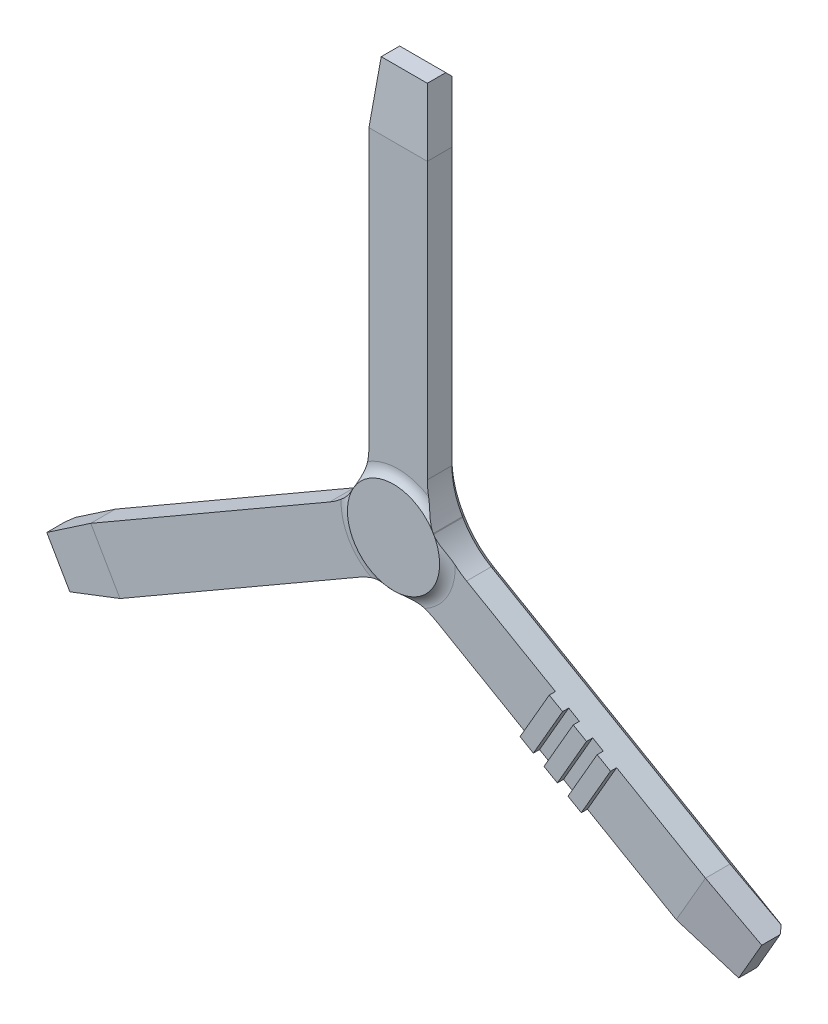
SolidWorks part; units mm, degrees
ref_plane "Front Plane" through (0, 0, 0) normal (0, 0, 1) x (1, 0, 0)
ref_plane "Top Plane" through (0, 0, 0) normal (0, 1, 0) x (1, 0, 0)
ref_plane "Right Plane" through (0, 0, 0) normal (1, 0, 0) x (0, 0, -1)
sketch "Sketch1" plane through (0, 0, 0) normal (0, 0, 1) x (1, 0, 0)
  line L0 (-1.9, 24) -> (1.9, 24) construction
  line L1 (0, 0) -> (0, 24) construction
  line L2 (-1.9, 24) -> (-1.9, 26)
  line L3 (-1.9, 26) -> (1.9, 26)
  line L4 (1.9, 26) -> (1.9, 24)
  line L5 (23.4667, -11.3546) -> (21.5667, -14.6454)
  line L6 (21.5667, -14.6454) -> (19.8346, -13.6454)
  line L7 (21.7346, -10.3546) -> (23.4667, -11.3546)
  line L8 (-21.5667, -14.6454) -> (-23.4667, -11.3546)
  line L9 (-23.4667, -11.3546) -> (-21.7346, -10.3546)
  line L10 (-19.8346, -13.6454) -> (-21.5667, -14.6454)
  line L11 (0, 0) -> (1.9, 24) construction
  line L12 (0, 0) -> (19.8346, -13.6454) construction
  line L13 (-1.9, 24) -> (-1.9, 1.097)
  line L14 (-1.9, 1.097) -> (-21.7346, -10.3546)
  line L15 (-19.8346, -13.6454) -> (0, -2.1939)
  line L16 (0, -2.1939) -> (19.8346, -13.6454)
  line L17 (21.7346, -10.3546) -> (1.9, 1.097)
  line L18 (1.9, 1.097) -> (1.9, 24)
  circle A0 centre (0, 0) radius 24 construction
  dimension "D1" = 48
  dimension "D2" = 3.8
  dimension "D3" = 2
  dimension "D4" = 120
  dimension "D5" = 24.0751
  dimension "D6" = 3
extrude "Boss-Extrude1" add sketch "Sketch1" along normal blind 2 contours L18 A0 L13 L14 L15 L16 L17 region at (0, 0, 0)
chamfer "Chamfer1" distance 4 distance2 0.4 3 edges at (22.5167, -13, 2) (-22.5167, -13, 2) (0, 26, 2) first distance on face at (0, 0, 2)
chamfer "Chamfer2" distance 0.4 distance2 4 3 edges at (23.4667, -11.3546, 0.8) (-1.9, 26, 0.8) (-21.5667, -14.6454, 0.8) first distance on face at (22.5167, -13, 0.8) first distance on face at (0, 26, 0.8) first distance on face at (-22.5167, -13, 0.8)
chamfer "Chamfer3" distance 4 distance2 0.4 3 edges at (1.9, 26, 0.8) (21.5667, -14.6454, 0.8) (-23.4667, -11.3546, 0.8) first distance on face at (1.9, 15.2388, 1.12) first distance on face at (12.2472, -9.2648, 1.12) first distance on face at (-14.1472, -5.9739, 1.12)
sketch "Sketch2" plane through (0, 0, 0) normal (0, 0, -1) x (-1, 0, 0)
  circle A0 centre (0, 0) radius 3
  dimension "D1" = 6
extrude "Boss-Extrude2" add sketch "Sketch2" against normal blind 2.3
fillet "Fillet1" radius 5 6 edges at (1.9, 2.3216, 1) (2.9606, 0.4846, 1) (1.0606, -2.8063, 1) (-1.0606, -2.8063, 1) (-2.9606, 0.4846, 1) (-1.9, 2.3216, 1)
fillet "Fillet2" radius 1 3 edges at (0, 3, 2) (2.5981, -1.5, 2) (-2.5981, -1.5, 2)
chamfer "Chamfer4" distance 0.4 angle 45 18 edges at (22.5167, -13, 0) (-22.5167, -13, 0) (0, 26, 0) (12.2293, -4.8667, 0) (3.4082, 0.4282, 0) (2.5981, 1.5, 0) (2.0749, 2.7374, 0) (1.9, 13.0242, 0) (-12.2293, -4.8667, 0) (-3.4082, 0.4282, 0) (-2.5981, 1.5, 0) (-2.0749, 2.7374, 0) (-1.9, 13.0242, 0) (10.3293, -8.1576, 0) (1.3332, -3.1657, 0) (0, -3, 0) (-1.3332, -3.1657, 0) (-10.3293, -8.1576, 0)
sketch "Sketch3" plane through (0, 0, 2) normal (0, 0, 1) x (1, 0, 0)
  line L0 (12.2293, -4.8667) -> (10.3293, -8.1576) construction
  line L3 (20.0026, -9.3546) -> (4.4561, -0.3788) construction
  line L5 (2.5561, -3.6697) -> (18.1026, -12.6454) construction
  line L7 (11.7963, -4.6167) -> (9.8963, -7.9076)
  line L8 (11.7963, -4.6167) -> (12.6623, -5.1167)
  line L9 (9.8963, -7.9076) -> (10.7623, -8.4076)
  line L10 (12.6623, -5.1167) -> (10.7623, -8.4076)
  line L11 (11.7963, -4.6167) -> (10.7623, -8.4076) construction
  line L12 (9.8963, -7.9076) -> (12.6623, -5.1167) construction
  line L13 (13.3551, -5.5167) -> (14.2212, -6.0167)
  line L14 (13.3551, -5.5167) -> (11.4551, -8.8076)
  line L15 (14.2212, -6.0167) -> (12.3212, -9.3076)
  line L16 (11.4551, -8.8076) -> (12.3212, -9.3076)
  line L29 (10.2375, -3.7167) -> (11.1035, -4.2167)
  line L30 (10.2375, -3.7167) -> (8.3375, -7.0076)
  line L31 (11.1035, -4.2167) -> (9.2035, -7.5076)
  line L32 (8.3375, -7.0076) -> (9.2035, -7.5076)
  line L465 (18.0317, -8.2167) -> (18.8977, -8.7167) [skipped]
  line L466 (18.0317, -8.2167) -> (16.1317, -11.5076) [skipped]
  line L467 (18.8977, -8.7167) -> (16.9977, -12.0076) [skipped]
  line L468 (16.1317, -11.5076) -> (16.9977, -12.0076) [skipped]
  line L469 (5.5609, -1.0167) -> (6.4269, -1.5167) [skipped]
  line L470 (5.5609, -1.0167) -> (3.6609, -4.3076) [skipped]
  line L471 (6.4269, -1.5167) -> (4.5269, -4.8076) [skipped]
  line L472 (3.6609, -4.3076) -> (4.5269, -4.8076) [skipped]
  line L473 (16.4728, -7.3167) -> (17.3389, -7.8167) [skipped]
  line L474 (16.4728, -7.3167) -> (14.5728, -10.6076) [skipped]
  line L475 (17.3389, -7.8167) -> (15.4389, -11.1076) [skipped]
  line L476 (14.5728, -10.6076) -> (15.4389, -11.1076) [skipped]
  line L477 (7.1198, -1.9167) -> (7.9858, -2.4167) [skipped]
  line L478 (7.1198, -1.9167) -> (5.2198, -5.2076) [skipped]
  line L479 (7.9858, -2.4167) -> (6.0858, -5.7076) [skipped]
  line L480 (5.2198, -5.2076) -> (6.0858, -5.7076) [skipped]
  line L481 (14.914, -6.4167) -> (15.78, -6.9167) [skipped]
  line L482 (14.914, -6.4167) -> (13.014, -9.7076) [skipped]
  line L483 (15.78, -6.9167) -> (13.88, -10.2076) [skipped]
  line L484 (13.014, -9.7076) -> (13.88, -10.2076) [skipped]
  line L485 (8.6786, -2.8167) -> (9.5446, -3.3167) [skipped]
  line L486 (8.6786, -2.8167) -> (6.7786, -6.1076) [skipped]
  line L487 (9.5446, -3.3167) -> (7.6446, -6.6076) [skipped]
  line L488 (6.7786, -6.1076) -> (7.6446, -6.6076) [skipped]
  point P7 (11.2793, -6.5121)
  dimension "D1" = 1
extrude "Boss-Extrude3" add sketch "Sketch3" along normal blind 0.4
